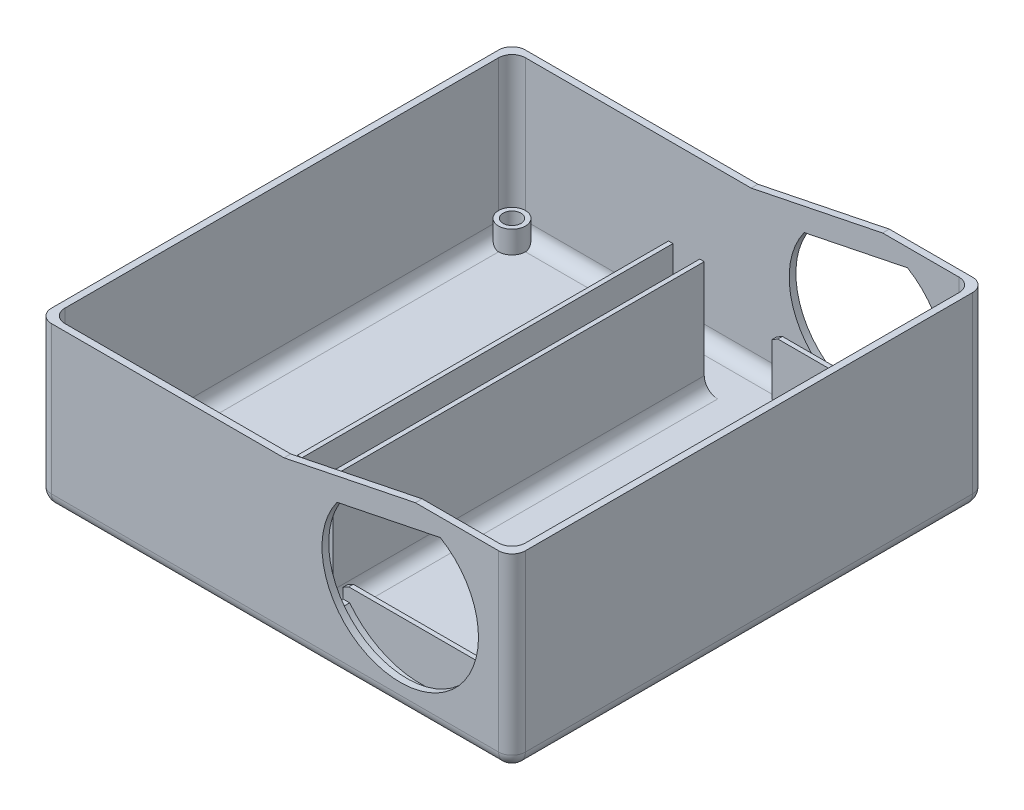
SolidWorks part; units mm, degrees
ref_plane "前视基准面" through (0, 0, 0) normal (0, 0, 1) x (1, 0, 0)
ref_plane "上视基准面" through (0, 0, 0) normal (0, 1, 0) x (1, 0, 0)
ref_plane "右视基准面" through (0, 0, 0) normal (1, 0, 0) x (0, 0, -1)
sketch "草图1" plane through (0, 0, 0) normal (0, 1, 0) x (1, 0, 0)
  line L1 (-53, 53) -> (53, 53)
  line L2 (-53, 53) -> (-53, -53)
  line L3 (-53, -53) -> (53, -53)
  line L4 (53, 53) -> (53, -53)
  line L5 (-53, 53) -> (53, -53) construction
  line L6 (-53, -53) -> (53, 53) construction
  point P0 (0, 0)
  dimension "D1" = 106
  dimension "D2" = 106
extrude "凸台-拉伸1" add sketch "草图1" along normal blind 42
shell "抽壳1" thickness 1.5 removed face at (0, 42, 0)
sketch "草图3" plane through (0, 1.5, 0) normal (0, 1, 0) x (1, 0, 0)
  line L0 (51.5, 51.5) -> (-51.5, 51.5) construction
  line L2 (-6.5, 41.5) -> (-6.5, -41.5)
  line L4 (1.5, 41.5) -> (1.5, -41.5)
  line L5 (-51.5, -51.5) -> (51.5, -51.5) construction
  line L6 (1.5, 41.5) -> (0.5, 41.5)
  line L7 (0.5, 41.5) -> (0.5, -41.5)
  line L10 (51.5, -51.5) -> (51.5, 51.5) construction
  line L11 (-51.5, 51.5) -> (-51.5, -51.5) construction
  line L12 (0.5, -41.5) -> (1.5, -41.5)
  line L15 (-6.5, -41.5) -> (-5.5, -41.5)
  line L16 (-5.5, -41.5) -> (-5.5, 41.5)
  line L17 (-5.5, 41.5) -> (-6.5, 41.5)
  dimension "D3" = 1
  dimension "D1" = 50
  dimension "D2" = 45
  dimension "D4" = 1
  dimension "D5" = 10
  dimension "D6" = 10
extrude "凸台-拉伸4" add sketch "草图3" along normal blind 25
fillet "圆角2" radius 3 12 edges at (51.5, 21.75, -51.5) (-51.5, 21.75, -51.5) (-51.5, 21.75, 51.5) (51.5, 21.75, 51.5) (0, 0, 53) (53, 0, 0) (-53, 0, 0) (0, 0, -53) (-53, 21, -53) (53, 21, -53) (53, 21, 53) (-53, 21, 53)
sketch "草图6" plane through (0, 0, 53) normal (0, 0, 1) x (1, 0, 0)
  line L0 (-53, 36) -> (2, 36)
  line L1 (-53, 3) -> (-53, 42) construction
  line L2 (2, 36) -> (31.3939, 42)
  line L3 (-50, 42) -> (50, 42) construction
  line L4 (31.3939, 42) -> (-53, 42)
  line L5 (-53, 42) -> (-53, 36)
  line L6 (-50, 3) -> (50, 3) construction
  dimension "D1" = 33
  dimension "D2" = 30
  dimension "D3" = 55
extrude "切除-拉伸3" cut sketch "草图6" against normal through all
sketch "草图7" plane through (0, 0, 53) normal (0, 0, 1) x (1, 0, 0)
  line L0 (53, 42) -> (53, 3) construction
  line L1 (50, 0) -> (-50, 0) construction
  line L2 (13.8661, 33.3191) -> (36.959, 38.0329)
  line L3 (2, 36) -> (31.3939, 42) construction
  arc A0 (13.8661, 33.3191) -> (36.959, 38.0329) centre (28, 23) ccw
  dimension "D1" = 35
  dimension "D2" = 25
  dimension "D3" = 23
  dimension "D4" = 5
extrude "切除-拉伸4" cut sketch "草图7" against normal through all
sketch "草图8" plane through (0, 0, 51.5) normal (0, 0, -1) x (-1, 0, 0)
  line L0 (-45.3205, 13) -> (-28, 23) construction
  line L1 (-28, 41) -> (-28, 3) construction
  line L2 (-10.6795, 13) -> (-28, 23) construction
  line L3 (-45.3205, 13) -> (-44.0215, 13.75)
  line L4 (-11.9785, 13.75) -> (-10.6795, 13)
  line L5 (-45.3205, 13) -> (-45.3205, 1.5)
  line L6 (48.5, 1.5) -> (-48.5, 1.5) construction
  line L7 (-45.3205, 1.5) -> (-10.6795, 1.5)
  line L8 (-10.6795, 1.5) -> (-10.6795, 13)
  line L9 (-44.0215, 13.75) -> (-11.9785, 13.75)
  arc A0 (-45.3205, 13) -> (-10.6795, 13) centre (-28, 23) ccw construction
  circle A1 centre (-28, 23) radius 17.5 construction
  arc A2 (-44.0215, 13.75) -> (-11.9785, 13.75) centre (-28, 23) ccw construction
  dimension "39" = 40
  dimension "D3" = 37
  dimension "D2" = 120
extrude "凸台-拉伸5" add sketch "草图8" along normal blind 4
sketch "草图10" plane through (0, 0, 51.5) normal (0, 0, -1) x (-1, 0, 0)
  line L0 (-45.3205, 13) -> (-28, 23)
  line L1 (-28, 3) -> (-28, 43) construction
  line L2 (-10.6795, 13) -> (-28, 23)
  arc A0 (-45.3205, 13) -> (-10.6795, 13) centre (-28, 23) ccw
  circle A1 centre (-28, 23) radius 17.5 construction
  dimension "D1" = 40
  dimension "D2" = 120
extrude "切除-拉伸7" cut sketch "草图10" along normal blind 3
mirror "镜向1" about plane through (0, 0, 0) normal (0, 0, 1) of "切除-拉伸7", "凸台-拉伸5"
sketch "草图17" plane through (0, 1.5, 0) normal (0, 1, 0) x (1, 0, 0)
  line L0 (1.5, 41.5) -> (0.5, 41.5) construction
  line L1 (0.5, 41.5) -> (0.5, -41.5) construction
  line L2 (0.5, -41.5) -> (1.5, -41.5) construction
  line L3 (1.5, -41.5) -> (1.5, 41.5) construction
  line L4 (-5.5, 41.5) -> (-6.5, 41.5) construction
  line L5 (-6.5, 41.5) -> (-6.5, -41.5) construction
  line L6 (-6.5, -41.5) -> (-5.5, -41.5) construction
  line L7 (-5.5, -41.5) -> (-5.5, 41.5) construction
  line L8 (1.5, 41.5) -> (0.5, 41.5)
  line L9 (0.5, 41.5) -> (0.5, -41.5)
  line L10 (0.5, -41.5) -> (1.5, -41.5)
  line L11 (1.5, -41.5) -> (1.5, 41.5)
  line L12 (10.6795, 47.5) -> (10.6795, 51.5)
  line L13 (10.6795, 51.5) -> (-48.5, 51.5)
  line L14 (-51.5, 48.5) -> (-51.5, -48.5)
  line L16 (10.6795, -51.5) -> (10.6795, -47.5)
  line L17 (10.6795, -47.5) -> (45.3205, -47.5)
  line L18 (45.3205, -47.5) -> (45.3205, -51.5)
  line L19 (45.3205, -51.5) -> (48.5, -51.5)
  line L20 (51.5, -48.5) -> (51.5, 48.5)
  line L21 (48.5, 51.5) -> (45.3205, 51.5)
  line L22 (45.3205, 51.5) -> (45.3205, 47.5)
  line L23 (45.3205, 47.5) -> (10.6795, 47.5)
  line L24 (10.6795, 47.5) -> (10.6795, 51.5)
  line L25 (10.6795, 51.5) -> (-48.5, 51.5)
  line L28 (10.6795, -51.5) -> (10.6795, -47.5)
  line L29 (10.6795, -47.5) -> (45.3205, -47.5)
  line L30 (45.3205, -47.5) -> (45.3205, -51.5)
  line L31 (45.3205, -51.5) -> (48.5, -51.5)
  line L32 (51.5, -48.5) -> (51.5, 48.5)
  line L33 (48.5, 51.5) -> (45.3205, 51.5)
  line L34 (45.3205, 51.5) -> (45.3205, 47.5)
  line L35 (45.3205, 47.5) -> (10.6795, 47.5)
  line L36 (-5.5, 41.5) -> (-6.5, 41.5)
  line L37 (-6.5, 41.5) -> (-6.5, -41.5)
  line L38 (-6.5, -41.5) -> (-5.5, -41.5)
  line L39 (-5.5, -41.5) -> (-5.5, 41.5)
  line L52 (-51.5, 48.5) -> (-51.5, -48.5)
  line L54 (-48.5, -51.5) -> (10.6795, -51.5)
  line L55 (-48.5, -51.5) -> (10.6795, -51.5)
  arc A4 (-48.5, 51.5) -> (-51.5, 48.5) centre (-48.5, 48.5) ccw
  arc A5 (-48.5, 51.5) -> (-51.5, 48.5) centre (-48.5, 48.5) ccw
  arc A6 (48.5, -51.5) -> (51.5, -48.5) centre (48.5, -48.5) ccw
  arc A7 (51.5, 48.5) -> (48.5, 51.5) centre (48.5, 48.5) ccw
  arc A10 (48.5, -51.5) -> (51.5, -48.5) centre (48.5, -48.5) ccw
  arc A11 (51.5, 48.5) -> (48.5, 51.5) centre (48.5, 48.5) ccw
  arc A12 (-51.5, -48.5) -> (-48.5, -51.5) centre (-48.5, -48.5) ccw
  arc A13 (-51.5, -48.5) -> (-48.5, -51.5) centre (-48.5, -48.5) ccw
  dimension "D1" = 0
extrude "切除-拉伸12" cut sketch "草图17" against normal blind 0.1
sketch "草图18" plane through (0, 1.4, 0) normal (0, 1, 0) x (1, 0, 0)
  circle A0 centre (-48.5, 48.5) radius 2
  circle A1 centre (-48.5, 48.5) radius 3
  circle A2 centre (48.5, 48.5) radius 2
  circle A3 centre (48.5, 48.5) radius 3
  arc A4 (-48.5, 51.5) -> (-51.5, 48.5) centre (-48.5, 48.5) ccw construction
  arc A5 (51.5, 48.5) -> (48.5, 51.5) centre (48.5, 48.5) ccw construction
  dimension "D1" = 4
  dimension "D2" = 6
  dimension "D3" = 4
  dimension "D4" = 6
extrude "凸台-拉伸6" add sketch "草图18" along normal blind 5
mirror "镜向2" about plane through (0, 0, 0) normal (0, 0, 1) of "凸台-拉伸6"
fillet "圆角3" radius 3 6 edges at (46.9103, 1.4, 51.5) (51.5, 1.4, 0) (46.9103, 1.4, -51.5) (-18.9103, 1.4, -51.5) (-18.9103, 1.4, 51.5) (-51.5, 1.4, 0)
sketch "草图22" plane through (0, 13.75, 0) normal (0, 1, 0) x (1, 0, 0)
  line L0 (45.3205, 48.5) -> (10.6795, 48.5) construction
  line L1 (10.6795, 51.5) -> (13.6795, 51.5)
  line L2 (10.6795, 51.5) -> (10.6795, 48.5)
  line L3 (10.6795, 48.5) -> (13.6795, 48.5)
  line L4 (13.6795, 51.5) -> (13.6795, 48.5)
  line L5 (11.9785, 48.5) -> (44.0215, 48.5) construction
  dimension "D1" = 3
extrude "切除-拉伸13" cut sketch "草图22" against normal blind 3
sketch "草图23" plane through (0, 13.75, 0) normal (0, 1, 0) x (1, 0, 0)
  line L0 (45.3205, 48.5) -> (12.1906, 48.5) construction
  line L1 (45.3205, 51.5) -> (42.3205, 51.5)
  line L2 (45.3205, 51.5) -> (45.3205, 48.5)
  line L3 (45.3205, 48.5) -> (42.3205, 48.5)
  line L4 (42.3205, 51.5) -> (42.3205, 48.5)
  dimension "D1" = 3
extrude "切除-拉伸14" cut sketch "草图23" against normal blind 3
mirror "镜向3" about plane through (0, 0, 0) normal (0, 0, 1) of "切除-拉伸13", "切除-拉伸14"
fillet "圆角4" radius 3 4 edges at (-6.5, 1.4, 0) (-5.5, 1.4, 0) (0.5, 1.4, 0) (1.5, 1.4, 0)
